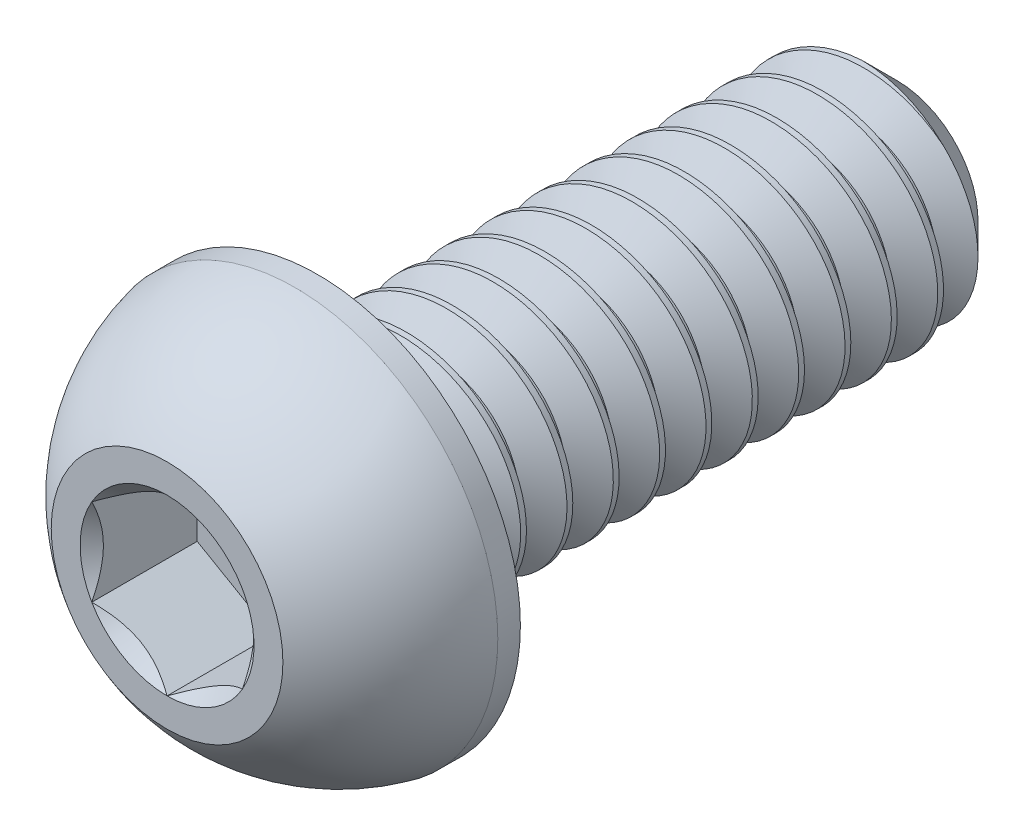
SolidWorks part; units mm, degrees
note: '?' marks a value the reader was unsure of.
ref_plane "Front" through (0, 0, 0) normal (0, 0, 1) x (1, 0, 0)
ref_plane "Top" through (0, 0, 0) normal (0, 1, 0) x (1, 0, 0)
ref_plane "Right" through (0, 0, 0) normal (1, 0, 0) x (0, 0, -1)
sketch "Sketch1" plane through (0, 0, 0) normal (1, 0, 0) x (0, 0, -1)
  line L2 (1.3, 1) -> (6.3, 1)
  line L3 (6.3, 1) -> (6.3, 0)
  line L4 (6.3, 0) -> (1.3, 0)
  line L6 (1.105, 1.75) -> (1.3, 1.75) construction
  line L7 (6.3, 1) -> (6.3, -1) construction
  line L8 (0, 0) -> (1.3, 0) construction
  line L9 (1.3, 1.75) -> (1.3, -1.75) construction
  line L11 (1.3, 1) -> (1.3, 0)
  line L13 (0, 0.65) -> (0, -0.65) construction
  line L14 (0, 0.65) -> (0, 1) construction
  arc A3 (0, 1) -> (1.105, 1.75) centre (1.4858, 0) cw construction
  dimension "D1" = 0.195
  dimension "Head Ht" = 1.3
  dimension "Head Dia" = 3.5
  dimension "Dia" = 2
  dimension "Lg" = 5
  dimension "Hex" = 1.3
revolve "Revolve1" add sketch "Sketch1" angle 360 mid plane about L4
sketch "Sketch3" plane through (0, 0, -6.3) normal (0, 0, -1) x (-1, 0, 0)
  circle A0 centre (0, 0) radius 1
curve "Helix/Spiral1" pitch 0.4 height 5 turns 12.5
chamfer "Chamfer1" distance 0.3 angle 45 1 edges at (0, 1, -6.3)
sketch "Sketch7" plane through (0, 0, 0) normal (1, 0, 0) x (0, 0, -1)
  line L6 (1.105, 1.75) -> (1.3, 1.75) construction
  line L8 (0, 0) -> (1.3, 0) construction
  line L11 (1.3, 1.75) -> (1.3, -1.75) construction
  line L12 (1.105, 1.75) -> (1.3, 1.75)
  line L13 (0, 0) -> (1.3, 0)
  line L14 (0, 0.65) -> (0, -0.65) construction
  line L15 (1.3, 1.75) -> (1.3, 0)
  line L16 (0, 1) -> (0, 0)
  arc A2 (1.105, 1.75) -> (0, 1) centre (1.4858, 0) ccw construction
  arc A3 (1.105, 1.75) -> (0, 1) centre (1.4858, 0) ccw
revolve "Revolve2" add sketch "Sketch7" angle 360 mid plane about L13
sketch "Sketch5" plane through (0, 0, 0) normal (0, 0, 1) x (1, 0, 0)
  line L1 (0.65, -0.3753) -> (0.65, 0.3753)
  line L2 (0.65, 0.3753) -> (0, 0.7506)
  line L3 (0, 0.7506) -> (-0.65, 0.3753)
  line L4 (-0.65, 0.3753) -> (-0.65, -0.3753)
  line L5 (-0.65, -0.3753) -> (0, -0.7506)
  line L6 (0, -0.7506) -> (0.65, -0.3753)
  circle A0 centre (0, 0) radius 0.65 construction
extrude "Cut-Extrude2" cut sketch "Sketch5" against normal blind 0.91
sketch "Sketch6" plane through (0, 0, 0) normal (0, 0, 1) x (1, 0, 0)
  circle A0 centre (0, 0) radius 0.7506
extrude "Cut-Extrude3" cut sketch "Sketch6" against normal blind 0.91 draft 45
sketch "Sketch2" plane through (0, 0, 0) normal (1, 0, 0) x (0, 0, -1)
  line L0 (6, 1) -> (6.35, 1)
  line L1 (6.35, 1) -> (6.2, 0.7402)
  line L2 (6.2, 0.7402) -> (6.15, 0.7402)
  line L3 (6.15, 0.7402) -> (6, 1)
  line L4 (6.075, 0.8701) -> (6.275, 0.8701) construction
  dimension "D1" = 60
  dimension "D2" = 0.05
  dimension "D3" = 0.2
sweep "Cut-Sweep1" cut profiles "Sketch2" path "Helix/Spiral1"
ref_axis "Center Axis 1" through (0, 0, -6.6675) along (0, 0, 1)?
ref_plane "Contact Plane 1" through (0, 0, -1.3) normal (0, 0, -1) x (-1, 0, 0)
ref_plane "Contact Plane 2" through (0, 0, 0) normal (0, 0, 1) x (1, 0, 0)
equation "\"D3@Helix/Spiral1\" = \"Lg@Sketch1\""
equation "\"D2@Sketch2\" = \"D4@Helix/Spiral1\" * .125"
equation "\"D3@Sketch2\" = \"D4@Helix/Spiral1\" * .5"
equation "\"D1@Chamfer1\" = \"D4@Helix/Spiral1\" * .75"
equation "\"D1@Cut-Extrude2\" = \"Head Ht@Sketch1\" * .7"
equation "\"D1@Sketch1\" = \"Head Ht@Sketch1\" * .15"
equation "\"D1@Cut-Extrude3\" = \"D1@Cut-Extrude2\""
